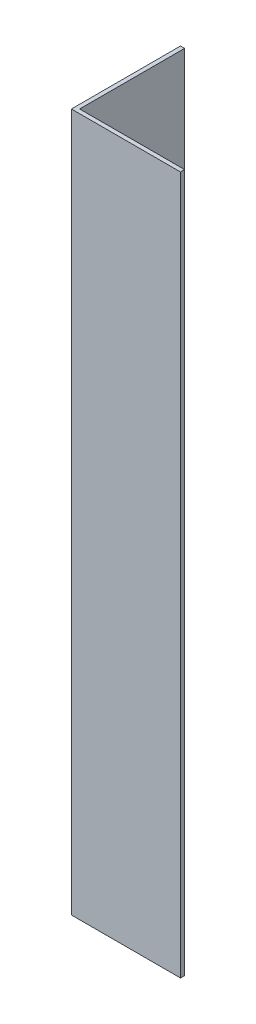
SolidWorks part; units mm, degrees
material "1060 Сплав"
ref_plane "Спереди" through (0, 0, 0) normal (0, 0, 1) x (1, 0, 0)
ref_plane "Сверху" through (0, 0, 0) normal (0, 1, 0) x (1, 0, 0)
ref_plane "Справа" through (0, 0, 0) normal (1, 0, 0) x (0, 0, -1)
sketch "Эскиз1" plane through (0, 0, 0) normal (0, 1, 0) x (1, 0, 0)
  line L0 (0, 0) -> (0, 20)
  line L1 (0, 20) -> (0.75, 20)
  line L2 (0.75, 20) -> (0.75, 0.75)
  line L3 (0.75, 0.75) -> (20, 0.75)
  line L4 (20, 0.75) -> (20, 0)
  line L5 (20, 0) -> (0, 0)
  dimension "D1" = 0.75
  dimension "D2" = 20
extrude "Бобышка-Вытянуть1" add sketch "Эскиз1" along normal blind 128
